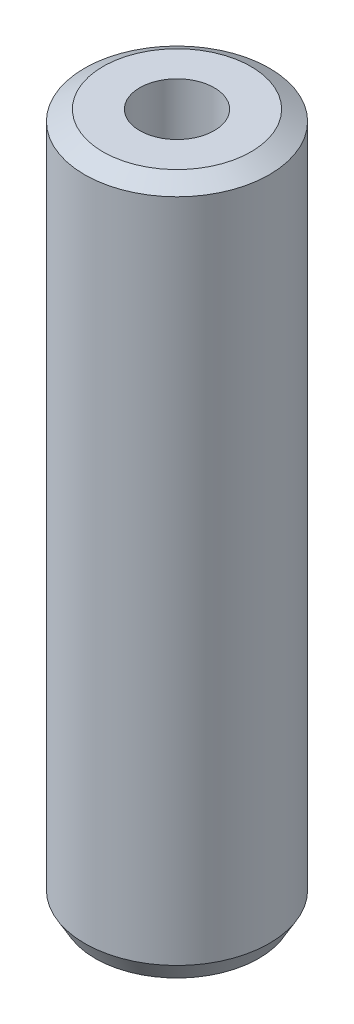
SolidWorks part; units mm, degrees
ref_plane "Front Plane" through (0, 0, 0) normal (0, 0, 1) x (1, 0, 0)
ref_plane "Top Plane" through (0, 0, 0) normal (0, 1, 0) x (1, 0, 0)
ref_plane "Right Plane" through (0, 0, 0) normal (1, 0, 0) x (0, 0, -1)
sketch "Sketch1" plane through (0, 0, 0) normal (0, 1, 0) x (1, 0, 0)
  circle A0 centre (0, 0) radius 35
  dimension "SHAFT_OD" = 70
extrude "Boss-Extrude1" add sketch "Sketch1" along normal blind 263.2539
sketch "Sketch2" plane through (0, 0, 0) normal (0, 1, 0) x (1, 0, 0)
  circle A0 centre (0, 0) radius 14.1128
  dimension "BORE_D" = 28.2256
extrude "Cut-Extrude1" cut sketch "Sketch2" along normal through all
chamfer "Chamfer1" distance 4.0162 angle 60 2 edges at (0, 263.2539, 35) (0, 0, 35) first distance on face at (0, 263.2539, 35) first distance on face at (0, 0, 14.1128)
